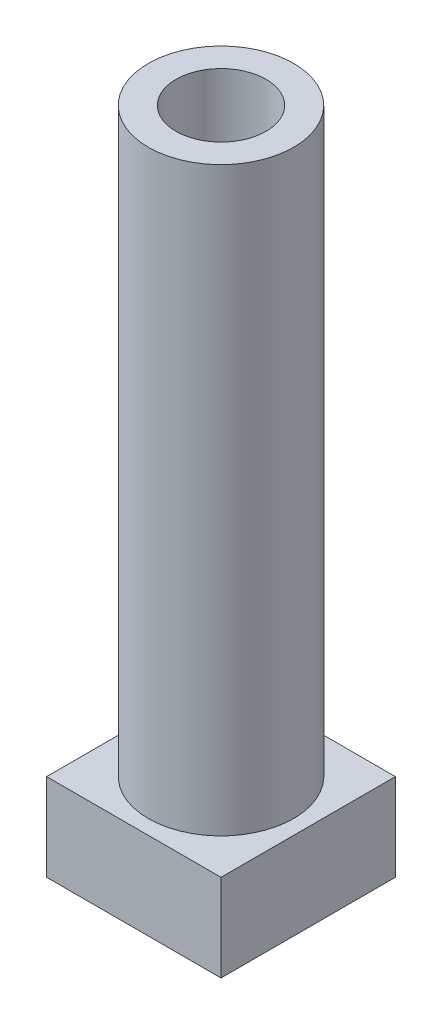
SolidWorks part; units mm, degrees
ref_plane "Front Plane" through (0, 0, 0) normal (0, 0, 1) x (1, 0, 0)
ref_plane "Top Plane" through (0, 0, 0) normal (0, 1, 0) x (1, 0, 0)
ref_plane "Right Plane" through (0, 0, 0) normal (1, 0, 0) x (0, 0, -1)
sketch "Sketch1" plane through (0, 0, 0) normal (0, 1, 0) x (1, 0, 0)
  line L1 (-3, -3) -> (3, -3)
  line L2 (-3, -3) -> (-3, 3)
  line L3 (-3, 3) -> (3, 3)
  line L4 (3, -3) -> (3, 3)
  line L5 (-3, -3) -> (3, 3) construction
  line L6 (-3, 3) -> (3, -3) construction
  circle A0 centre (0, 0) radius 2.5
  circle A1 centre (0, 0) radius 1.55
  point P0 (0, 0)
  dimension "D1" = 5
  dimension "D3" = 3.1
  dimension "D2" = 3
extrude "Boss-Extrude1" add sketch "Sketch1" against normal blind 3 contours L1 L4 L3 L2 A0 | A0 A1 | A1 region at (-2.9151, 0, 0) region at (-2.4293, 0, 0) region at (0, 0, 0)
extrude "Boss-Extrude2" add sketch "Sketch1<3>" along normal blind 3 contours A1 region at (0, 0, 0)
sketch "Sketch1<3>" plane through (0, 0, 0) normal (0, 1, 0) x (1, 0, 0) same geometry as "Sketch1"
extrude "Boss-Extrude3" add sketch "Sketch1<4>" along normal blind 20 contours A0 A1 region at (-2.4293, 0, 0)
sketch "Sketch1<4>" plane through (0, 0, 0) normal (0, 1, 0) x (1, 0, 0) same geometry as "Sketch1"
